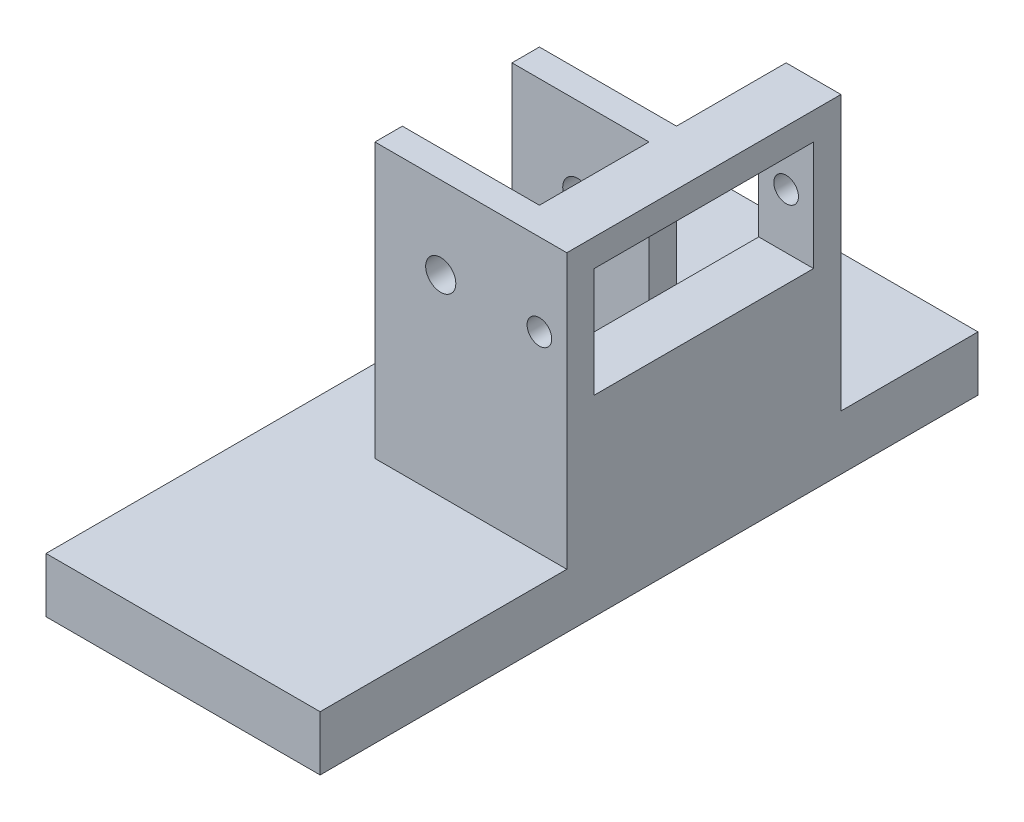
SolidWorks part; units mm, degrees
ref_plane "Front Plane" through (0, 0, 0) normal (0, 0, 1) x (1, 0, 0)
ref_plane "Top Plane" through (0, 0, 0) normal (0, 1, 0) x (1, 0, 0)
ref_plane "Right Plane" through (0, 0, 0) normal (1, 0, 0) x (0, 0, -1)
sketch "Sketch4" plane through (0, 0, 0) normal (0, 1, 0) x (1, 0, 0)
  line L1 (0, 0) -> (40, 0)
  line L2 (0, 0) -> (0, 80)
  line L3 (0, 80) -> (40, 80)
  line L4 (40, 0) -> (40, 80)
  dimension "D1" = 80
  dimension "D2" = 40
extrude "Boss-Extrude4" add sketch "Sketch4" along normal blind 5
sketch "Sketch5" plane through (0, 5, 0) normal (0, 1, 0) x (1, 0, 0)
  line L0 (40, 40) -> (30, 40)
  line L1 (30, 30) -> (30, 50) construction
  line L2 (40, 50) -> (30, 50)
  line L3 (30, 50) -> (30, 55)
  line L4 (0, 80) -> (0, 0)
  line L5 (0, 0) -> (40, 0)
  line L6 (40, 0) -> (40, 80)
  line L7 (40, 80) -> (0, 80)
  line L8 (0, 80) -> (0, 0)
  line L9 (0, 0) -> (40, 0)
  line L10 (40, 0) -> (40, 80)
  line L11 (40, 80) -> (0, 80)
  line L12 (30, 55) -> (40, 55)
  line L13 (40, 55) -> (40, 50)
  line L14 (40, 30) -> (30, 30)
  line L15 (30, 30) -> (30, 25)
  line L16 (30, 25) -> (40, 25)
  line L17 (40, 25) -> (40, 30)
  point P9 (30, 40)
  line M11 (40, 0) -> (40, 80)
  dimension "D2" = 10
  dimension "D3" = 10
  dimension "D4" = 5
  dimension "D5" = 5
  dimension "D1" = 0
extrude "Boss-Extrude6" add sketch "Sketch5" along normal blind 50 contours L12 L3 L2 M11 | L15 L16 L10 L14 region at (35, 5, -52.5) region at (35, 5, -27.5)
sketch "Sketch7" plane through (0, 0, -50) normal (0, 0, 1) x (1, 0, 0)
  line L1 (30, 5) -> (40, 5)
  line L2 (30, 5) -> (30, 30)
  line L3 (30, 30) -> (40, 30)
  line L4 (40, 5) -> (40, 30)
  line L5 (40, 55) -> (40, 5) construction
  line L7 (30, 55) -> (40, 55)
  line L8 (30, 55) -> (30, 50)
  line L9 (30, 50) -> (40, 50)
  line L10 (40, 55) -> (40, 50)
  dimension "D1" = 25
  dimension "D2" = 10
  dimension "D3" = 5
extrude "Boss-Extrude7" add sketch "Sketch7" along normal up to surface (20 mm away) contours L8 L7 L10 L9 | L2 L1 L4 L3 up to face at (35, 30, -30)
sketch "Sketch9" plane through (0, 0, 0) normal (-1, 0, 0) x (0, 0, 1)
  line L4 (-80, 0) -> (0, 0)
  line L5 (0, 0) -> (0, 5)
  line L6 (0, 5) -> (-80, 5)
  line L7 (-80, 5) -> (-80, 0)
  line L8 (-80, 0) -> (0, 0)
  line L9 (0, 0) -> (0, 5)
  line L10 (0, 5) -> (-80, 5)
  line L12 (-80, 5) -> (-80, 0)
  dimension "D1" = 0
extrude "Boss-Extrude9" add sketch "Sketch9" along normal blind 10
sketch "Sketch10" plane through (0, 0, 0) normal (0, 0, 1) x (1, 0, 0)
  line L4 (-10, 0) -> (40, 0)
  line L5 (40, 0) -> (40, 5)
  line L6 (40, 5) -> (-10, 5)
  line L7 (-10, 5) -> (-10, 0)
  line L8 (-10, 0) -> (40, 0)
  line L9 (40, 0) -> (40, 5)
  line L10 (40, 5) -> (-10, 5)
  line L11 (-10, 5) -> (-10, 0)
  dimension "D1" = 0
extrude "Boss-Extrude10" add sketch "Sketch10" along normal blind 20
sketch "Sketch11" plane through (0, 0, -50) normal (0, 0, 1) x (1, 0, 0)
  line L0 (30, 40) -> (35, 40)
  line L4 (30, 30) -> (40, 30)
  line L5 (40, 30) -> (40, 50)
  line L6 (40, 50) -> (30, 50)
  line L7 (30, 50) -> (30, 30)
  line L8 (30, 30) -> (40, 30)
  line L9 (40, 30) -> (40, 50)
  line L10 (40, 50) -> (30, 50)
  line L11 (30, 50) -> (30, 30)
  circle A0 centre (35, 40) radius 2.25
  dimension "D3" = 4.5
  dimension "D2" = 5
  dimension "D1" = 0
extrude "Cut-Extrude1" cut sketch "Sketch11" against normal mid plane 50 contours A0 region at (35, 42.1864, -50)
sketch "Sketch12" plane through (0, 0, -25) normal (0, 0, 1) x (1, 0, 0)
  circle A0 centre (35, 40) radius 2.25 construction
  circle A1 centre (35, 40) radius 2.25
  circle A2 centre (35, 40) radius 4
  dimension "D1" = 8
extrude "Cut-Extrude2" cut sketch "Sketch12" against normal blind 2
sketch "Sketch15" plane through (30, 0, 0) normal (-1, 0, 0) x (0, 0, 1)
  line L1 (-55, 55) -> (-50, 55)
  line L2 (-55, 55) -> (-55, 5)
  line L3 (-55, 5) -> (-50, 5)
  line L4 (-50, 55) -> (-50, 5)
  line L5 (-25, 55) -> (-30, 55)
  line L6 (-25, 55) -> (-25, 5)
  line L7 (-25, 5) -> (-30, 5)
  line L8 (-30, 55) -> (-30, 5)
  dimension "D1" = 50
  dimension "D2" = 5
  dimension "D3" = 50
  dimension "D4" = 5
extrude "Boss-Extrude11" add sketch "Sketch15" along normal blind 20
sketch "Sketch16" plane through (0, 0, -25) normal (0, 0, 1) x (1, 0, 0)
  line L0 (35, 40) -> (17, 40)
  circle A0 centre (35, 40) radius 4 construction
  circle A1 centre (35, 40) radius 4
  circle A2 centre (17, 40) radius 2.75
  dimension "D2" = 5.5
  dimension "D1" = 18
extrude "Cut-Extrude4" cut sketch "Sketch16" against normal up to surface (30 mm away) contours A2 region at (14.3278, 40, -25) up to face at (32.75, 40, -55)
sketch "Sketch19" plane through (10, 0, 0) normal (-1, 0, 0) x (0, 0, 1)
  line L4 (-55, 55) -> (-55, 5)
  line L5 (-55, 5) -> (-50, 5)
  line L6 (-50, 5) -> (-50, 55)
  line L7 (-50, 55) -> (-55, 55)
  line L8 (-55, 55) -> (-55, 5)
  line L10 (-50, 5) -> (-50, 55)
  line L11 (-50, 55) -> (-55, 55)
  line L12 (-25, 5) -> (-25, 55)
  line L13 (-25, 55) -> (-30, 55)
  line L14 (-30, 55) -> (-30, 5)
  line L15 (-30, 5) -> (-25, 5)
  line L16 (-25, 5) -> (-25, 55)
  line L17 (-25, 55) -> (-30, 55)
  line L18 (-30, 55) -> (-30, 5)
  line L20 (-55, 5) -> (-50, 5)
  line L21 (-30, 5) -> (-25, 5)
  dimension "D1" = 0
  dimension "D2" = 0
extrude "Boss-Extrude12" add sketch "Sketch19" along normal blind 5
sketch "Sketch21" plane through (0, 0, 0) normal (0, -1, 0) x (1, 0, 0)
  line L4 (40, -80) -> (40, 20)
  line L5 (40, 20) -> (-10, 20)
  line L6 (-10, 20) -> (-10, -80)
  line L7 (-10, -80) -> (40, -80)
  line L8 (40, -80) -> (40, 20)
  line L9 (40, 20) -> (-10, 20)
  line L10 (-10, 20) -> (-10, -80)
  line L11 (-10, -80) -> (40, -80)
  dimension "D1" = 0
extrude "Boss-Extrude14" add sketch "Sketch21" along normal blind 5
sketch "Sketch22" plane through (0, 0, -80) normal (0, 0, -1) x (-1, 0, 0)
  line L4 (-40, 5) -> (-40, -5)
  line L5 (-40, -5) -> (10, -5)
  line L6 (10, -5) -> (10, 5)
  line L7 (10, 5) -> (-40, 5)
  line L8 (-40, 5) -> (-40, -5)
  line L9 (-40, -5) -> (10, -5)
  line L10 (10, -5) -> (10, 5)
  line L11 (10, 5) -> (-40, 5)
  dimension "D1" = 0
extrude "Boss-Extrude15" add sketch "Sketch22" along normal blind 20
sketch "Sketch24" plane through (0, 55, 0) normal (0, 1, 0) x (1, 0, 0)
  line L1 (5, 55) -> (40, 55)
  line L2 (5, 55) -> (5, 50)
  line L3 (5, 50) -> (40, 50)
  line L4 (40, 55) -> (40, 50)
  line L5 (40, 25) -> (40, 55) construction
  dimension "D1" = 35
  dimension "D2" = 5
extrude "Cut-Extrude5" cut sketch "Sketch24" against normal blind 50
sketch "Sketch25" plane through (0, 0, -50) normal (0, 0, -1) x (-1, 0, 0)
  line L4 (-30, 5) -> (-30, 30)
  line L5 (-30, 30) -> (-40, 30)
  line L6 (-40, 30) -> (-40, 5)
  line L7 (-40, 5) -> (-30, 5)
  line L8 (-30, 5) -> (-30, 30)
  line L9 (-30, 30) -> (-40, 30)
  line L10 (-40, 30) -> (-40, 5)
  line L11 (-40, 5) -> (-30, 5)
  line L12 (-30, 50) -> (-30, 55)
  line L13 (-30, 55) -> (-40, 55)
  line L14 (-40, 55) -> (-40, 50)
  line L15 (-40, 50) -> (-30, 50)
  line L16 (-30, 50) -> (-30, 55)
  line L17 (-30, 55) -> (-40, 55)
  line L18 (-40, 55) -> (-40, 50)
  line L19 (-40, 50) -> (-30, 50)
  dimension "D1" = 0
  dimension "D2" = 0
extrude "Boss-Extrude16" add sketch "Sketch25" along normal blind 25
sketch "Sketch26" plane through (0, 30, 0) normal (0, 1, 0) x (1, 0, 0)
  line L1 (40, 75) -> (30, 75)
  line L2 (40, 75) -> (40, 70)
  line L3 (40, 70) -> (30, 70)
  line L4 (30, 75) -> (30, 70)
  line L5 (30, 30) -> (30, 75) construction
  dimension "D1" = 5
  dimension "D2" = 10
extrude "Boss-Extrude17" add sketch "Sketch26" along normal blind 20
sketch "Sketch27" plane through (0, 0, -27) normal (0, 0, 1) x (1, 0, 0)
  circle A0 centre (35, 40) radius 2.25 construction
  circle A1 centre (35, 40) radius 4
  circle A2 centre (35, 40) radius 4
  circle A3 centre (35, 40) radius 2.25
  dimension "D1" = 0
extrude "Boss-Extrude18" add sketch "Sketch27" along normal up to surface (2 mm away) up to face at (19.75, 40, -25)
sketch "Sketch28" plane through (0, 0, -25) normal (0, 0, 1) x (1, 0, 0)
  circle A0 centre (35, 40) radius 2.25 construction
  circle A1 centre (35, 40) radius 2.25
extrude "Cut-Extrude6" cut sketch "Sketch28" against normal blind 50
sketch "Sketch29" plane through (0, 5, 0) normal (0, 1, 0) x (1, 0, 0)
  line L0 (5, 30) -> (5, 50) construction
  line L2 (5, 50) -> (30, 50)
  line L3 (5, 50) -> (5, 55)
  line L4 (5, 55) -> (30, 55)
  line L5 (30, 50) -> (30, 55)
  line L6 (30, 30) -> (30, 75) construction
  dimension "D1" = 20
  dimension "D2" = 5
  dimension "D3" = 25
extrude "Boss-Extrude19" add sketch "Sketch29" along normal up to surface (50 mm away) contours L3 L2 L5 L4 up to face at (25, 55, -43.3333)
sketch "Sketch31" plane through (0, 0, -25) normal (0, 0, 1) x (1, 0, 0)
  circle A0 centre (17, 40) radius 2.75 construction
  circle A1 centre (17, 40) radius 2.75
extrude "Cut-Extrude7" cut sketch "Sketch31" against normal blind 30
